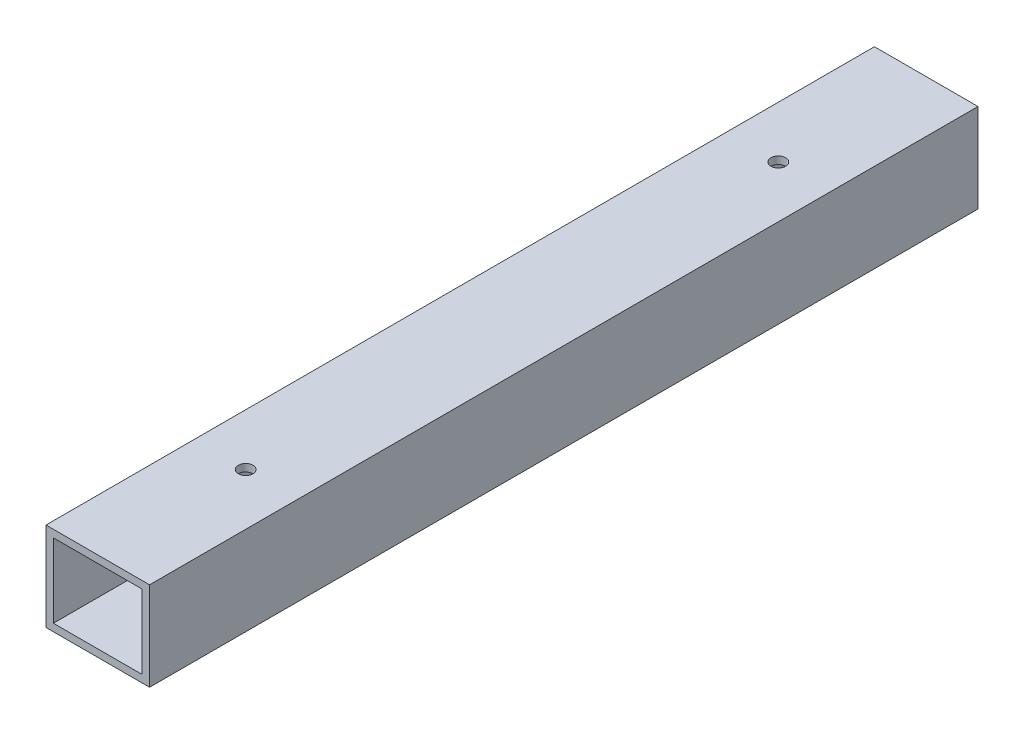
SolidWorks part; units mm, degrees
ref_plane "Front Plane" through (0, 0, 0) normal (0, 0, 1) x (1, 0, 0)
ref_plane "Top Plane" through (0, 0, 0) normal (0, 1, 0) x (1, 0, 0)
ref_plane "Right Plane" through (0, 0, 0) normal (1, 0, 0) x (0, 0, -1)
sketch "Sketch1" plane through (0, 0, 0) normal (0, 0, 1) x (1, 0, 0)
  line L0 (22.225, 0) -> (19.05, 0) construction
  line L1 (-22.225, 0) -> (22.225, 0) construction
  line L2 (0, 19.05) -> (0, -19.05)
  point P7 (0, 0)
sketch "Sketch2" plane through (0, 0, 0) normal (1, 0, 0) x (0, 0, -1)
  line L0 (177.8, 0) -> (-177.8, 0)
  point P4 (0, 0)
  dimension "Length" = 355.6
sketch "Sketch3" plane through (0, 0, 0) normal (0, 0, 1) x (1, 0, 0)
  line L0 (-22.225, 0) -> (22.225, 0) construction
  line L5 (22.225, -19.05) -> (-22.225, -19.05)
  line L6 (22.225, -19.05) -> (22.225, 19.05)
  line L11 (22.225, 19.05) -> (-22.225, 19.05)
  line L12 (-22.225, -19.05) -> (-22.225, 19.05)
  line L14 (22.225, -19.05) -> (-22.225, 19.05) construction
  line L15 (22.225, 19.05) -> (-22.225, -19.05) construction
  line L16 (19.05, -15.875) -> (-19.05, -15.875)
  line L17 (19.05, -15.875) -> (19.05, 15.875)
  line L18 (19.05, 15.875) -> (-19.05, 15.875)
  line L19 (-19.05, -15.875) -> (-19.05, 15.875)
  line L20 (19.05, -15.875) -> (-19.05, 15.875) construction
  line L21 (19.05, 15.875) -> (-19.05, -15.875) construction
  point P0 (0, 0)
  point P5 (0, 0)
  point P13 (19.05, -19.05)
  dimension "D1" = 3.175
  dimension "D3" = 44.45
  dimension "D4" = 38.1
  dimension "D2" = 3.175
extrude "Boss-Extrude1" add sketch "Sketch3" along normal up to vertex (177.8 mm away) and the other way up to vertex (177.8 mm away) up to point (0, 0, 177.8) other way up to point (0, 0, -177.8)
sketch "Sketch5" plane through (0, 0, 0) normal (1, 0, 0) x (0, 0, -1)
  line L0 (-177.8, 0) -> (177.8, 0) construction
  line L3 (-177.8, -19.05) -> (-177.8, 19.05) construction
  line L4 (177.8, -19.05) -> (177.8, 19.05) construction
  point P6 (-127.7937, 0)
  point P7 (-111.125, 0)
  point P8 (111.125, 0)
  point P10 (127.7937, 0)
  dimension "D1" = 50.0062
  dimension "D2" = 66.675
  dimension "D3" = 50.0062
  dimension "D4" = 66.675
sketch "Sketch6" plane through (0, 19.05, 0) normal (0, 1, 0) x (1, 0, 0)
  line L0 (22.225, -177.8) -> (-22.225, -177.8) construction
  line L1 (22.225, 177.8) -> (-22.225, 177.8) construction
  circle A0 centre (0, -114.3) radius 3.175
  circle A1 centre (0, 114.3) radius 3.175
  dimension "D3" = 6.35
  dimension "D1" = 63.5
  dimension "D2" = 63.5
extrude "Cut-Extrude1" cut sketch "Sketch6" against normal through all
equation "\"D1@Sketch3\"=\"Wall thickness@Sketch1\""
equation "\"D1@Sketch5\"=\"Width@Sketch1\"*1.125"
equation "\"D2@Sketch5\"=\"Width@Sketch1\"*1.5"
equation "\"D3@Sketch5\"=\"D1@Sketch5\""
equation "\"D4@Sketch5\"=\"D2@Sketch5\""
equation "\"D2@Sketch3\"=\"Wall Thickness@Sketch1\""
